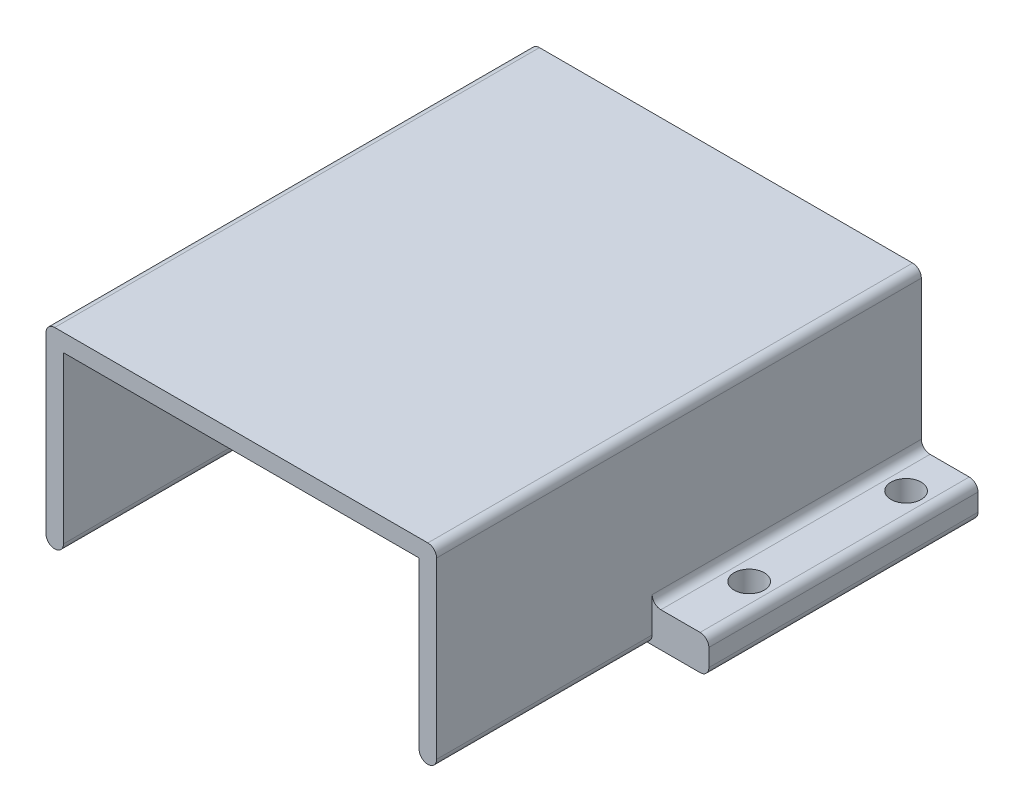
SolidWorks part; units mm, degrees
ref_plane "Front Plane" through (0, 0, 0) normal (0, 0, 1) x (1, 0, 0)
ref_plane "Top Plane" through (0, 0, 0) normal (0, 1, 0) x (1, 0, 0)
ref_plane "Right Plane" through (0, 0, 0) normal (1, 0, 0) x (0, 0, -1)
sketch "Sketch1" plane through (0, 0, 0) normal (0, 0, 1) x (1, 0, 0)
  line L0 (0, 0) -> (0, 25.4) construction
  line L1 (25.908, 25.4) -> (-25.908, 25.4)
  line L2 (-25.908, 25.4) -> (-25.908, 0)
  line L3 (-25.908, 0) -> (-36.703, 0)
  line L4 (-36.703, 0) -> (-36.703, 5.08)
  line L5 (-36.703, 5.08) -> (-28.448, 5.08)
  line L6 (-28.448, 5.08) -> (-28.448, 27.94)
  line L7 (-28.448, 27.94) -> (28.448, 27.94)
  line L9 (28.448, 5.08) -> (28.448, 27.94)
  line L10 (36.703, 5.08) -> (28.448, 5.08)
  line L11 (36.703, 0) -> (36.703, 5.08)
  line L12 (25.908, 0) -> (36.703, 0)
  line L13 (25.908, 25.4) -> (25.908, 0)
  point P6 (0, 25.4)
  point P12 (0, 27.94)
  dimension "D1" = 25.4
  dimension "D2" = 25.908
  dimension "D3" = 5.08
  dimension "D4" = 2.54
  dimension "D5" = 36.703
  dimension "D6" = 2.54
extrude "Boss-Extrude1" add sketch "Sketch1" along normal blind 70.612
sketch "Sketch2" plane through (0, 5.08, 0) normal (0, 1, 0) x (1, 0, 0)
  line L0 (-28.448, 0) -> (-36.703, 0) construction
  line L1 (-32.5755, 0) -> (-32.5755, -70.612) construction
  line L2 (-28.448, -70.612) -> (-36.703, -70.612) construction
  circle A0 centre (-32.5755, -6.35) radius 2.2
  circle A1 centre (-32.5755, -29.21) radius 2.2
  dimension "D1" = 4.4
  dimension "D3" = 22.86
  dimension "D4" = 6.35
extrude "Cut-Extrude1" cut sketch "Sketch2" against normal through all
mirror "Mirror1" about plane through (0, 0, 0) normal (1, 0, 0) of "Cut-Extrude1"
sketch "Sketch3" plane through (0, 5.08, 0) normal (0, 1, 0) x (1, 0, 0)
  line L0 (-36.703, -39.2106) -> (-28.448, -39.2106)
  line L1 (-36.703, -70.612) -> (-36.703, 0) construction
  line L2 (-28.448, -70.612) -> (-28.448, 0) construction
  line L3 (-28.448, -39.2106) -> (-28.448, -70.612)
  line L4 (-28.448, -70.612) -> (-36.703, -70.612)
  line L5 (-36.703, -70.612) -> (-36.703, -39.2106)
  line L6 (0, 0) -> (0, -70.612) construction
  line L7 (28.448, -70.612) -> (-28.448, -70.612) construction
  line L8 (36.703, -70.612) -> (36.703, -39.2106)
  line L9 (28.448, -70.612) -> (36.703, -70.612)
  line L10 (28.448, -39.2106) -> (28.448, -70.612)
  line L11 (36.703, -39.2106) -> (28.448, -39.2106)
extrude "Cut-Extrude2" cut sketch "Sketch3" against normal through all
sketch "Sketch6" plane through (0, 0, 0) normal (0, 0, -1) x (-1, 0, 0)
  line L0 (-25.908, 0) -> (25.908, 0)
  line L16 (25.908, 25.4) -> (25.908, 0)
  line L17 (25.908, 0) -> (36.703, 0)
  line L18 (36.703, 0) -> (36.703, 5.08)
  line L19 (36.703, 5.08) -> (28.448, 5.08)
  line L20 (28.448, 5.08) -> (28.448, 27.94)
  line L21 (28.448, 27.94) -> (-28.448, 27.94)
  line L22 (-28.448, 27.94) -> (-28.448, 5.08)
  line L23 (-28.448, 5.08) -> (-36.703, 5.08)
  line L24 (-36.703, 5.08) -> (-36.703, 0)
  line L25 (-36.703, 0) -> (-25.908, 0)
  line L26 (-25.908, 0) -> (-25.908, 25.4)
  line L27 (-25.908, 25.4) -> (25.908, 25.4)
  line L29 (25.908, 0) -> (36.703, 0)
  line L30 (36.703, 0) -> (36.703, 5.08)
  line L31 (36.703, 5.08) -> (28.448, 5.08)
  line L32 (28.448, 5.08) -> (28.448, 27.94)
  line L33 (28.448, 27.94) -> (-28.448, 27.94)
  line L34 (-28.448, 27.94) -> (-28.448, 5.08)
  line L35 (-28.448, 5.08) -> (-36.703, 5.08)
  line L36 (-36.703, 5.08) -> (-36.703, 0)
  line L37 (-36.703, 0) -> (-25.908, 0)
  dimension "D1" = 0
extrude "Boss-Extrude3" add sketch "Sketch6" against normal blind 2.54
sketch "Sketch4" plane through (0, 0, 70.612) normal (0, 0, 1) x (1, 0, 0)
  line L1 (-28.448, 0) -> (28.448, 0)
  line L2 (-28.448, 0) -> (-28.448, 27.94)
  line L3 (-28.448, 27.94) -> (28.448, 27.94)
  line L4 (28.448, 0) -> (28.448, 27.94)
sketch "Sketch8" plane through (0, 0, 0) normal (0, 0, -1) x (-1, 0, 0)
  line L0 (-15.875, 0) -> (15.875, 0) construction
  line L1 (-15.875, 0) -> (15.875, 0)
  arc A0 (-15.875, 0) -> (15.875, 0) centre (0, -12.6841) cw
  point P0 (0, 0)
  dimension "D1" = 20.32
  dimension "D2" = 31.75
extrude "Cut-Extrude6" cut sketch "Sketch8" against normal up to surface (2.54 mm away) up to face at (0, 12.7, 2.54)
sketch "Sketch9" plane through (0, 0, 0) normal (0, 0, -1) x (-1, 0, 0)
  line L0 (25.908, 25.4) -> (25.908, 0) construction
  line L1 (-25.908, 0) -> (25.908, 0)
  line L2 (-25.908, 0) -> (-25.908, 2.54)
  line L3 (-25.908, 2.54) -> (25.908, 2.54)
  line L4 (25.908, 0) -> (25.908, 2.54)
  dimension "D1" = 2.54
extrude "Cut-Extrude7" cut sketch "Sketch9" against normal up to surface (2.54 mm away) up to face at (0, 9.7393, 2.54)
fillet "Fillet1" radius 1.27 12 edges at (-28.448, 5.08, 19.6053) (28.448, 5.08, 19.6053) (36.703, 0, 19.6053) (36.703, 5.08, 19.6053) (-36.703, 5.08, 19.6053) (-36.703, 0, 19.6053) (28.448, 0, 54.9113) (25.908, 0, 35.306) (-25.908, 0, 35.306) (-28.448, 0, 54.9113) (28.448, 27.94, 35.306) (-28.448, 27.94, 35.306)
fillet "Fillet2" radius 1.27 2 edges at (-25.908, 2.54, 1.27) (25.908, 2.54, 1.27)
sketch "Sketch11" plane through (0, 0, 0) normal (0, 0, -1) x (-1, 0, 0)
  line L0 (28.448, 0) -> (28.448, 27.94) construction
  line L1 (1.905, 13.589) -> (18.415, 13.589)
  line L2 (1.905, 13.589) -> (1.905, 22.479)
  line L3 (1.905, 22.479) -> (18.415, 22.479)
  line L4 (18.415, 13.589) -> (18.415, 22.479)
  line L5 (1.905, 13.589) -> (18.415, 22.479) construction
  line L6 (1.905, 22.479) -> (18.415, 13.589) construction
  line L7 (28.448, 27.94) -> (-28.448, 27.94) construction
  point P0 (10.16, 18.034)
  dimension "D1" = 18.288
  dimension "D2" = 9.906
  dimension "D3" = 16.51
  dimension "D4" = 8.89
extrude "Cut-Extrude8" cut sketch "Sketch11" against normal up to surface (2.54 mm away) up to face at (0, 8.6402, 2.54)
